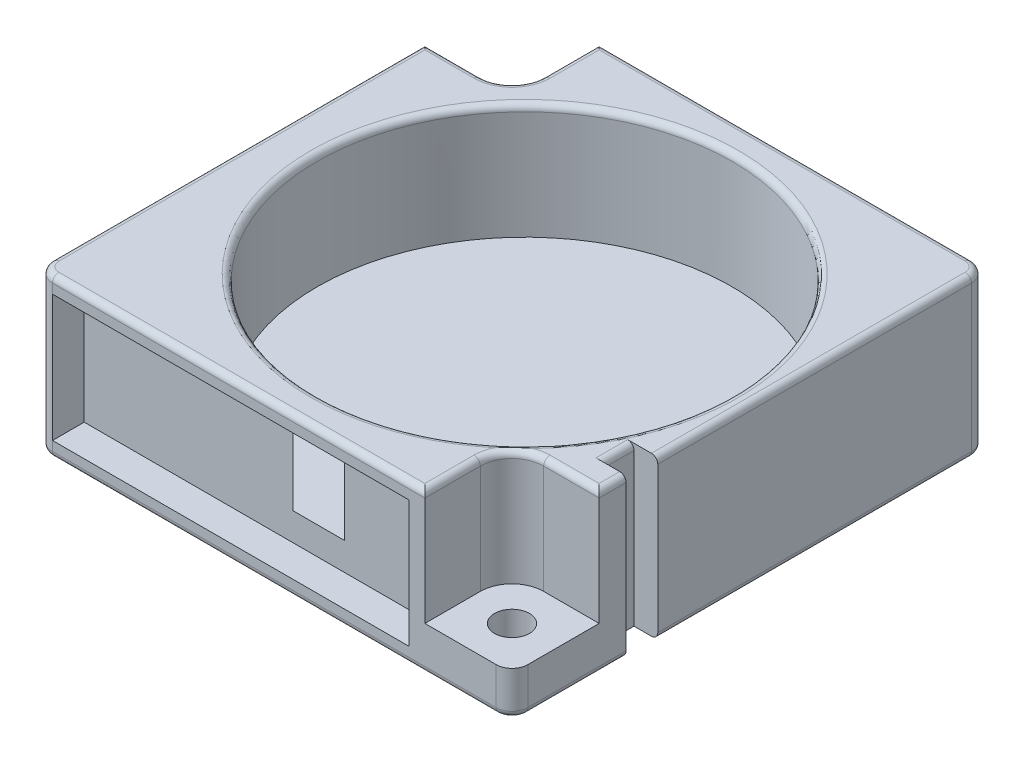
SolidWorks part; units mm, degrees
material "AISI 304"
ref_plane "Front Plane" through (0, 0, 0) normal (0, 0, 1) x (1, 0, 0)
ref_plane "Top Plane" through (0, 0, 0) normal (0, 1, 0) x (1, 0, 0)
ref_plane "Right Plane" through (0, 0, 0) normal (1, 0, 0) x (0, 0, -1)
sketch "Sketch1" plane through (0, 0, 0) normal (0, 1, 0) x (1, 0, 0)
  line L1 (0, 0) -> (30, 0)
  line L2 (0, 0) -> (0, -30)
  line L3 (0, -30) -> (30, -30)
  line L4 (30, 0) -> (30, -30)
  dimension "D1" = 30
  dimension "D2" = 30
extrude "Boss-Extrude1" add sketch "Sketch1" along normal blind 10
sketch "Sketch2" plane through (0, 10, 0) normal (0, 1, 0) x (1, 0, 0)
  line L1 (30, -30) -> (24.5, -30)
  line L2 (30, -30) -> (30, -24.5)
  line L3 (30, -24.5) -> (24.5, -24.5)
  line L4 (24.5, -30) -> (24.5, -24.5)
  line L5 (0, 0) -> (5.5, 0)
  line L6 (0, 0) -> (0, -5.5)
  line L7 (0, -5.5) -> (5.5, -5.5)
  line L8 (5.5, 0) -> (5.5, -5.5)
  dimension "D1" = 5.5
  dimension "D2" = 5.5
  dimension "D3" = 5.5
  dimension "D4" = 5.5
extrude "Cut-Extrude1" cut sketch "Sketch2" against normal blind 7.25
fillet "Fillet1" radius 2 2 edges at (5.5, 6.375, 5.5) (24.5, 6.375, 24.5)
sketch "Sketch3" plane through (0, 10, 0) normal (0, 1, 0) x (1, 0, 0)
  line L0 (30, -24.5) -> (30, 0) construction
  line L1 (30, 0) -> (5.5, 0) construction
  circle A0 centre (15.8, -15) radius 13.1
  dimension "D3" = 26.2
  dimension "D1" = 14.2
  dimension "D2" = 15
extrude "Cut-Extrude2" cut sketch "Sketch3" against normal blind 7.25
sketch "Sketch4" plane through (0, 2.75, 0) normal (0, 1, 0) x (1, 0, 0)
  line L0 (24.5, -30) -> (30, -30) construction
  line L1 (30, -30) -> (30, -24.5) construction
  line L2 (0, 0) -> (0, -5.5) construction
  line L3 (5.5, 0) -> (0, 0) construction
  circle A0 centre (2.75, -2.75) radius 1.1
  circle A1 centre (27.25, -27.25) radius 1.1
  dimension "D1" = 2.2
  dimension "D2" = 2.2
  dimension "D3" = 2.75
  dimension "D4" = 2.75
  dimension "D5" = 2.75
  dimension "D6" = 2.75
extrude "Cut-Extrude3" cut sketch "Sketch4" against normal through all
sketch "Sketch5" plane through (0, 0, 30) normal (0, 0, 1) x (1, 0, 0)
  line L0 (1, 9) -> (23.5, 9)
  line L1 (0, 0) -> (24.5, 0) construction
  line L2 (0, 0) -> (0, 10) construction
  line L3 (0, 10) -> (24.5, 10) construction
  line L4 (24.5, 0) -> (24.5, 10) construction
  line L5 (23.5, 1) -> (23.5, 9)
  line L6 (1, 1) -> (23.5, 1)
  line L7 (1, 1) -> (1, 9)
  dimension "D1" = 1
extrude "Cut-Extrude4" cut sketch "Sketch5" against normal blind 2
sketch "Sketch6" plane through (30, 0, 0) normal (1, 0, 0) x (0, 0, -1)
  line L0 (-24.5, 10) -> (0, 10) construction
  line L1 (-20.8, 10) -> (-22.8, 10)
  line L2 (-20.8, 10) -> (-20.8, 0)
  line L3 (-20.8, 0) -> (-22.8, 0)
  line L4 (-22.8, 10) -> (-22.8, 0)
  line L5 (-30, 0) -> (0, 0) construction
  line L6 (-30, 2.75) -> (-30, 0) construction
  dimension "D1" = 7.2
  dimension "D2" = 2
extrude "Cut-Extrude5" cut sketch "Sketch6" against normal blind 1.5
fillet "Fillet2" radius 1 4 edges at (30, 5, 0) (30, 1.375, 30) (0, 5, 30) (0, 1.375, 0)
fillet "Fillet3" radius 0.4 24 edges at (24.5, 10, 28.25) (25.0858, 10, 25.0858) (12.75, 10, 30) (0.2929, 10, 29.7071) (5.5, 10, 1.75) (4.9142, 10, 4.9142) (17.25, 10, 0) (29.7071, 10, 0.2929) (30, 0, 10.9) (29.7071, 0, 0.2929) (30, 0, 25.9) (29.7071, 0, 29.7071) (15, 0, 30) (0.2929, 0, 29.7071) (0, 0, 15) (0.2929, 0, 0.2929) (28.5, 10, 21.8) (30, 10, 23.65) (28.25, 10, 24.5) (0, 10, 17.25) (1.75, 10, 5.5) (30, 10, 10.9) (15, 0, 0) (15.8, 10, 28.1)
equation "\"D1@Cut-Extrude1\"=10-2.75"
equation "\"D4@Sketch4\"=\"D3@Sketch4\""
equation "\"D5@Sketch4\"=\"D3@Sketch4\""
equation "\"D6@Sketch4\"=\"D3@Sketch4\""
equation "\"D1@Sketch3\"=15-0.8"
